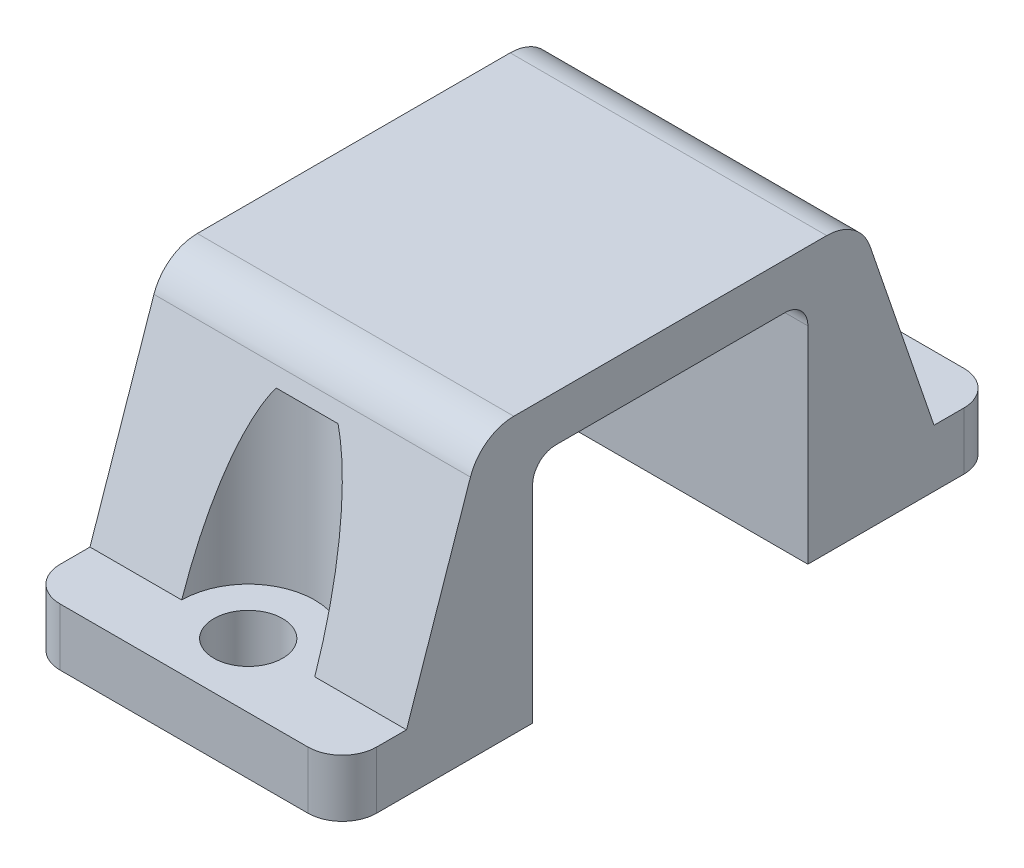
SolidWorks part; units mm, degrees
ref_plane "Alzado" through (0, 0, 0) normal (0, 0, 1) x (1, 0, 0)
ref_plane "Planta" through (0, 0, 0) normal (0, 1, 0) x (1, 0, 0)
ref_plane "Vista lateral" through (0, 0, 0) normal (1, 0, 0) x (0, 0, -1)
sketch "Croquis1" plane through (0, 0, 0) normal (1, 0, 0) x (0, 0, -1)
  line L0 (-6, 0) -> (6, 0)
  line L1 (6, 0) -> (6, -10)
  line L2 (14.3, -10) -> (6, -10)
  line L3 (14.3, -10) -> (14.3, -7.5)
  line L4 (14.3, -7.5) -> (11.5, -7.5)
  line L6 (8.25, 2) -> (-8.25, 2)
  line L7 (-6, 0) -> (-6, -10)
  line L8 (-6, -10) -> (-14.3, -10)
  line L9 (-14.3, -10) -> (-14.3, -7.5)
  line L10 (-14.3, -7.5) -> (-11.5, -7.5)
  line L12 (8.25, 2) -> (11.5, -7.5)
  line L13 (-8.25, 2) -> (-11.5, -7.5)
  point P4 (0, 0)
  point P12 (0, 2)
  dimension "D1" = 12
  dimension "D2" = 16.5
  dimension "D3" = 2.5
  dimension "D4" = 10
  dimension "D5" = 8.3
  dimension "D6" = 12
  dimension "D7" = 8.3
  dimension "D8" = 2.5
  dimension "D9" = 5.5
  dimension "D10" = 5.5
  dimension "D11" = 12
extrude "Saliente-Extruir1" add sketch "Croquis1" along normal blind 13.8
sketch "Croquis3" plane through (0, 0, 0) normal (0, 1, 0) x (1, 0, 0)
  line L0 (13.8, -11.5) -> (0, -11.5) construction
  line L5 (13.8, 11.5) -> (0, 11.5) construction
  circle A0 centre (6.9, -11.5) radius 1.5
  circle A1 centre (6.9, -11.5) radius 2.9
  circle A2 centre (6.9, 11.5) radius 2.9
  circle A3 centre (6.9, 11.5) radius 1.5
  point P5 (0, 0)
  point P10 (0, 0)
  dimension "D1" = 3
  dimension "D2" = 5.8
  dimension "D3" = 2
extrude "Cortar-Extruir1" cut sketch "Croquis3" against normal up to surface (10 mm away) contours A0 | A3 region at (6.9, 0, 11.5) region at (6.9, 0, -11.5) up to face at (6.9, -10, 10.15)
extrude "Cortar-Extruir2" cut sketch "Croquis3<3>" against normal up to surface (7.5 mm away) contours A1 A0 | A2 A3 region at (4.082, 0, 11.5) region at (4.082, 0, -11.5) up to face at (6.9, -7.5, 12.6833)
sketch "Croquis3<3>" plane through (0, 0, 0) normal (0, 1, 0) x (1, 0, 0) same geometry as "Croquis3"
fillet "Redondeo1" radius 1 2 edges at (6.9, 0, 6) (6.9, 0, -6)
fillet "Redondeo2" radius 2 2 edges at (6.9, 2, -8.25) (6.9, 2, 8.25)
fillet "Redondeo3" radius 1.5 4 edges at (0, -8.75, 14.3) (13.8, -8.75, 14.3) (13.8, -8.75, -14.3) (0, -8.75, -14.3)
